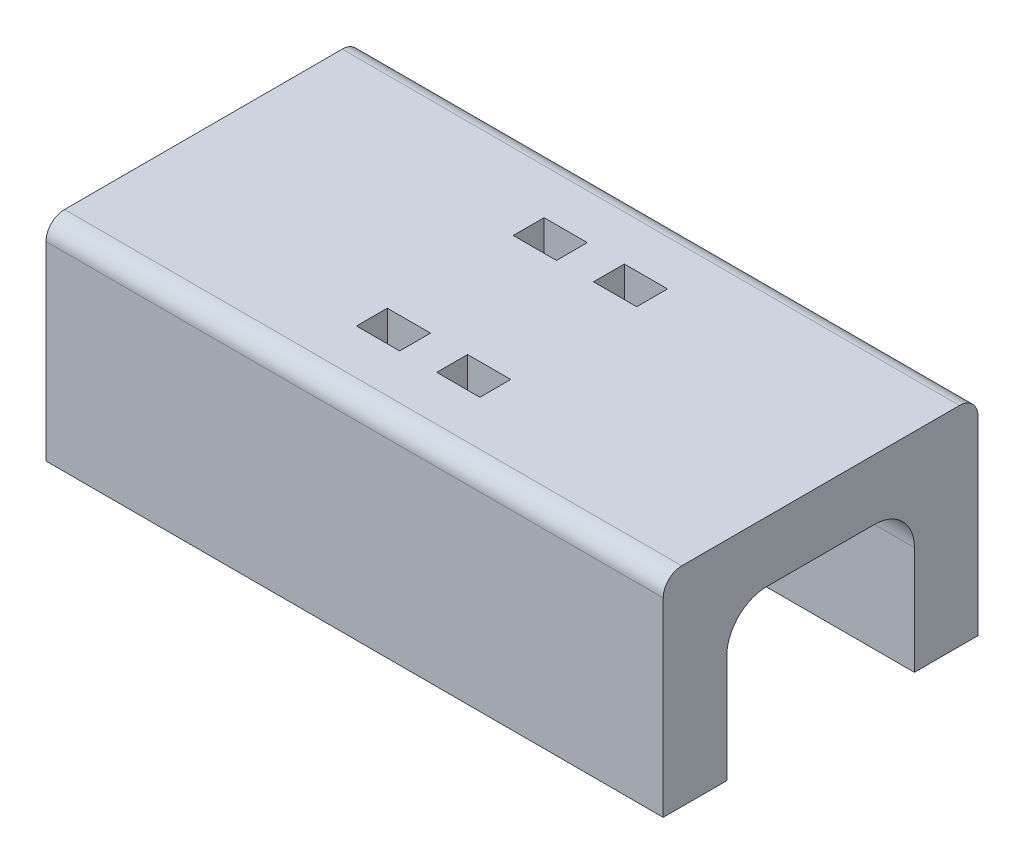
SolidWorks part; units mm, degrees
ref_plane "Front Plane" through (0, 0, 0) normal (0, 0, 1) x (1, 0, 0)
ref_plane "Top Plane" through (0, 0, 0) normal (0, 1, 0) x (1, 0, 0)
ref_plane "Right Plane" through (0, 0, 0) normal (1, 0, 0) x (0, 0, -1)
sketch "Sketch1" plane through (0, 0, 0) normal (0, 1, 0) x (1, 0, 0)
  line L1 (0, 0) -> (50, 0)
  line L2 (0, 0) -> (0, 25.5)
  line L3 (0, 25.5) -> (50, 25.5)
  line L4 (50, 0) -> (50, 25.5)
  dimension "D1" = 50
  dimension "D2" = 25.5
extrude "Boss-Extrude1" add sketch "Sketch1" along normal blind 16.9
sketch "Sketch3" plane through (0, 0, 0) normal (0, -1, 0) x (1, 0, 0)
  line L0 (50, 0) -> (50, -25.5) construction
  line L1 (0, -20.35) -> (50, -20.35)
  line L2 (0, -20.35) -> (0, -5.15)
  line L3 (0, -5.15) -> (50, -5.15)
  line L4 (50, -20.35) -> (50, -5.15)
  line L5 (0, -20.35) -> (50, -5.15) construction
  line L6 (0, -5.15) -> (50, -20.35) construction
  line L7 (0, 0) -> (50, 0) construction
  point P0 (25, -12.75)
  point P7 (25, 0)
  dimension "D1" = 50
  dimension "D2" = 15.2
  dimension "D3" = 12.75
extrude "Cut-Extrude1" cut sketch "Sketch3" against normal blind 12
sketch "Sketch4" plane through (0, 12, 0) normal (0, -1, 0) x (1, 0, 0)
  line L6 (50, -5.15) -> (0, -5.15) construction
  line L7 (20, -20.5) -> (30, -20.5)
  line L8 (20, -20.5) -> (20, -5.15)
  line L9 (20, -5.15) -> (30, -5.15)
  line L10 (30, -20.5) -> (30, -5.15)
  point P12 (25, -12.75)
  dimension "D1" = 10
extrude "Boss-Extrude2" add sketch "Sketch4" along normal blind 12
sketch "Sketch5" plane through (0, 0, 0) normal (0, -1, 0) x (1, 0, 0)
  line L1 (20, -5.15) -> (23.5, -5.15)
  line L2 (20, -5.15) -> (20, -7.65)
  line L3 (20, -7.65) -> (23.5, -7.65)
  line L4 (23.5, -5.15) -> (23.5, -7.65)
  line L5 (30, -5.15) -> (26.5, -5.15)
  line L6 (30, -5.15) -> (30, -7.65)
  line L7 (30, -7.65) -> (26.5, -7.65)
  line L8 (26.5, -5.15) -> (26.5, -7.65)
  line L9 (30, -20.35) -> (26.5, -20.35)
  line L10 (30, -20.35) -> (30, -17.85)
  line L11 (30, -17.85) -> (26.5, -17.85)
  line L12 (26.5, -20.35) -> (26.5, -17.85)
  line L13 (20, -20.35) -> (23.5, -20.35)
  line L14 (20, -20.35) -> (20, -17.85)
  line L15 (20, -17.85) -> (23.5, -17.85)
  line L16 (23.5, -20.35) -> (23.5, -17.85)
  dimension "D1" = 3.5
  dimension "D2" = 2.5
  dimension "D3" = 2.5
  dimension "D4" = 3.5
  dimension "D5" = 3.5
  dimension "D6" = 2.5
  dimension "D7" = 2.5
  dimension "D8" = 3.5
extrude "Cut-Extrude2" cut sketch "Sketch5" against normal through all
sketch "Sketch6" plane through (30, 0, 0) normal (1, 0, 0) x (0, 0, -1)
  circle A0 centre (12.75, 6) radius 2.75
  dimension "D1" = 5.5
extrude "Cut-Extrude3" cut sketch "Sketch6" against normal blind 2
sketch "Sketch7" plane through (20, 0, 0) normal (-1, 0, 0) x (0, 0, 1)
  circle A0 centre (-12.75, 6) radius 2.75
  dimension "D1" = 5.5
extrude "Cut-Extrude4" cut sketch "Sketch7" against normal blind 2
sketch "Sketch8" plane through (0, 0, 0) normal (0, -1, 0) x (1, 0, 0)
  line L0 (0, -2.575) -> (50, -2.575) construction
  line L10 (0, -5.15) -> (0, 0) construction
  line L12 (50, 0) -> (50, -5.15) construction
  line L13 (0, -22.925) -> (50, -22.925) construction
  line L14 (0, -25.5) -> (0, -20.35) construction
  line L15 (50, -20.35) -> (50, -25.5) construction
  line L16 (30, -17.85) -> (30, -7.65) construction
  line L17 (0, 0) -> (50, 0) construction
  circle A0 centre (25, -12.75) radius 1.15
  circle A1 centre (6.25, -2.575) radius 1.15
  circle A2 centre (43.75, -2.575) radius 1.15
  circle A3 centre (6.25, -22.925) radius 1.15
  circle A4 centre (43.75, -22.925) radius 1.15
  point P23 (30, -12.75)
  point P26 (25, 0)
  dimension "D1" = 2.3
  dimension "D2" = 2.3
  dimension "D3" = 2.3
  dimension "D4" = 2.3
  dimension "D5" = 2.3
  dimension "D6" = 6.25
  dimension "D7" = 6.25
  dimension "D8" = 6.25
  dimension "D9" = 6.25
  dimension "D10" = 5
  dimension "D11" = 12.75
extrude "Cut-Extrude5" cut sketch "Sketch8" against normal blind 10
fillet "Fillet2" radius 0.35 2 edges at (30, 6, -15.5) (20, 6, -10)
fillet "Fillet3" radius 3.25 4 edges at (10, 12, -20.35) (40, 12, -20.35) (40, 12, -5.15) (10, 12, -5.15)
fillet "Fillet4" radius 1 4 edges at (30, 5.9561, -17.85) (30, 5.9561, -7.65) (20, 5.9561, -7.65) (20, 5.9561, -17.85)
fillet "Fillet5" radius 1.5 2 edges at (25, 16.9, 0) (25, 16.9, -25.5)
sketch "Sketch9" plane through (0, 0, 0) normal (0, -1, 0) x (1, 0, 0)
  circle A0 centre (43.75, -22.925) radius 1.5
  circle A1 centre (6.25, -22.925) radius 1.5
  circle A2 centre (43.75, -2.575) radius 1.5
  circle A3 centre (6.25, -2.575) radius 1.5
  circle A4 centre (25, -12.75) radius 1.5
  dimension "D1" = 3
extrude "Cut-Extrude6" cut sketch "Sketch9" against normal blind 3
